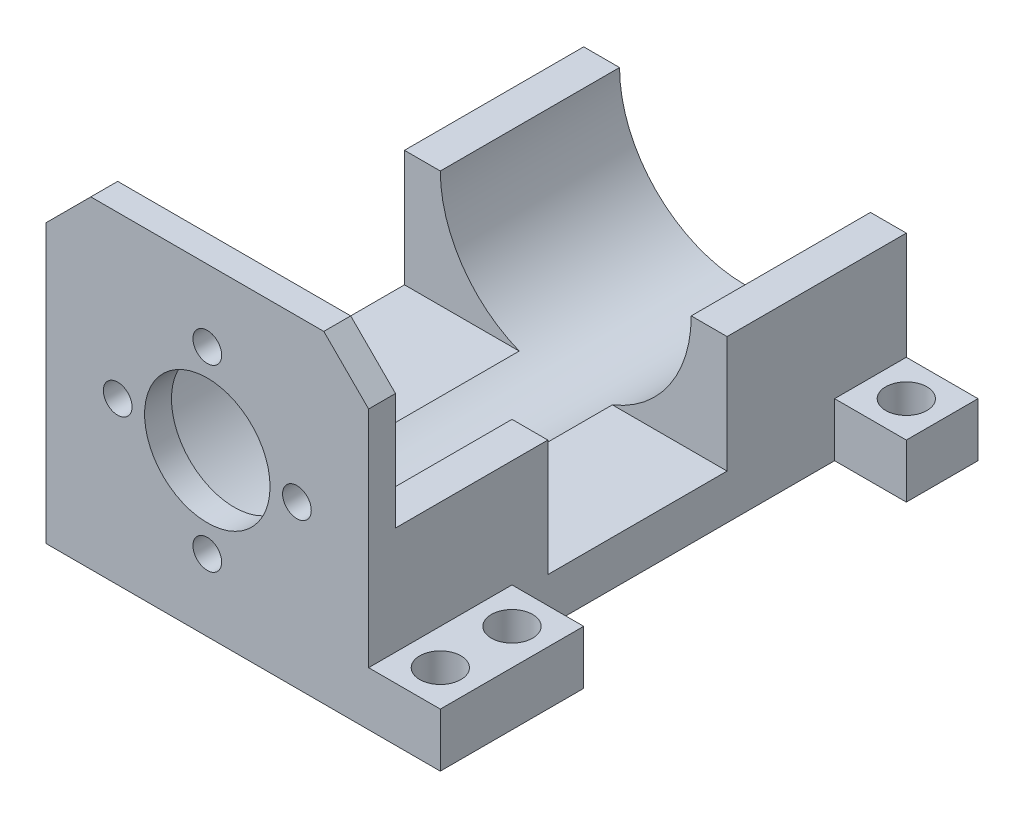
SolidWorks part; units mm, degrees
note: The reader was unsure of these and kept them because the rebuilt part matched: shared geometry of "Esquisse1<3>".
ref_plane "Plan de face" through (0, 0, 0) normal (0, 0, 1) x (1, 0, 0)
ref_plane "Plan de dessus" through (0, 0, 0) normal (0, 1, 0) x (1, 0, 0)
ref_plane "Plan de droite" through (0, 0, 0) normal (1, 0, 0) x (0, 0, -1)
sketch "Esquisse1" plane through (0, 0, 0) normal (0, 0, 1) x (1, 0, 0)
  line L0 (0, 0) -> (-10, 0) construction
  line L1 (-10, 0) -> (10, 0) construction
  line L2 (10, 0) -> (0, 0) construction
  line L3 (0, 0) -> (0, 10) construction
  line L4 (0, 0) -> (0, -10) construction
  line L5 (-18, 0) -> (-18, -18)
  line L6 (-18, -18) -> (0, -18)
  line L7 (0, -18) -> (18, -18)
  line L8 (18, -18) -> (18, 0)
  line L10 (18, 18) -> (-18, 18)
  line L11 (-18, 18) -> (-18, 0)
  line L12 (-18, 18) -> (-18, 13)
  line L13 (-18, 13) -> (-18, 18)
  line L14 (-18, 18) -> (-13, 18)
  line L15 (-13, 18) -> (-18, 13)
  line L16 (18, 18) -> (13, 18)
  line L17 (13, 18) -> (18, 18)
  line L18 (18, 18) -> (18, 13)
  line L19 (18, 13) -> (18, 0)
  line L20 (13, 18) -> (18, 13)
  line L21 (-18, 0) -> (-14, 0)
  line L22 (18, 0) -> (14, 0)
  circle A0 centre (0, 0) radius 14
  circle A1 centre (0, 0) radius 18
  circle A2 centre (-10, 0) radius 1.6
  circle A3 centre (0, 10) radius 1.6
  circle A4 centre (10, 0) radius 1.6
  circle A5 centre (0, -10) radius 1.6
  circle A6 centre (0, 0) radius 7
extrude "Boss.-Extru.1" add sketch "Esquisse1" against normal blind 60 contours A1 L7 L8 | A1 L5 L6 | L21 A1 L22 A0
extrude "Boss.-Extru.2" add sketch "Esquisse1<3>" against normal blind 3 contours A0 A5 A4 A3 A2 | L22 A1 L21 A0 | A1 L19 L20 L10 | A1 L10 L15 L11
sketch "Esquisse1<3>" plane through (0, 0, 0) normal (0, 0, 1) x (1, 0, 0) same geometry as "Esquisse1"
sketch "Esquisse2" plane through (0, -18, 0) normal (0, -1, 0) x (1, 0, 0)
  line L0 (18, 0) -> (26, 0)
  line L1 (26, 0) -> (26, -16)
  line L2 (26, -16) -> (18, -16)
  line L3 (18, -60) -> (18, 0) construction
  line L4 (18, -16) -> (18, 0)
  line L5 (18, -8) -> (26, -8) construction
  line L6 (26, -8) -> (18, 0) construction
  line L7 (26, 0) -> (18, -8) construction
  line L8 (18, -8) -> (26, -16) construction
  line L9 (18, -16) -> (26, -8) construction
  line L10 (26, -8) -> (18, -8) construction
  line L11 (18, -8) -> (18, -60)
  line L12 (18, -60) -> (26, -60)
  line L13 (26, -60) -> (26, -52)
  line L14 (26, -52) -> (18, -52)
  line L15 (18, -52) -> (18, -60) construction
  line L16 (18, -60) -> (26, -52) construction
  line L17 (26, -52) -> (18, -52) construction
  line L18 (18, -52) -> (26, -60) construction
  line L19 (26, -60) -> (-18, -60) construction
  line L20 (-18, -60) -> (-30, -60)
  line L21 (-30, -60) -> (-30, -52)
  line L22 (-30, -52) -> (-18, -52)
  line L23 (-18, -60) -> (-18, 0) construction
  line L24 (-18, -52) -> (-18, -60)
  line L25 (-30, -52) -> (-22, -52) construction
  line L26 (-30, -52) -> (-30, -60) construction
  line L27 (-22, -52) -> (-22, -60) construction
  line L28 (-22, -60) -> (-30, -52) construction
  line L29 (-30, -60) -> (-22, -52) construction
  circle A1 centre (22, -56) radius 2.3
  circle A2 centre (22, -12) radius 2.3
  circle A3 centre (22, -4) radius 2.3
  circle A4 centre (-26, -56) radius 2.3
sketch "Esquisse3" plane through (-18, 0, 0) normal (-1, 0, 0) x (0, 0, 1)
  line L0 (-60, -18) -> (0, -18) construction
  line L1 (-30, -18) -> (-30, 0) construction
  line L2 (-60, 0) -> (-3, 0) construction
  line L3 (-30, 0) -> (-20, 0)
  line L4 (-30, 0) -> (-40, 0)
  line L5 (-40, 0) -> (-40, -18) construction
  line L6 (-40, -18) -> (-30, -18) construction
  line L7 (-30, -18) -> (-20, -18) construction
  line L8 (-20, -18) -> (-20, 0) construction
  line L9 (-40, -18) -> (-40, -13) construction
  line L10 (-40, -13) -> (-20, -13)
  line L11 (-20, -13) -> (-20, 0)
  line L12 (-40, -13) -> (-40, 0)
extrude "Enlèv. mat.-Extru.2" cut sketch "Esquisse3" against normal blind 50
extrude "Boss.-Extru.4" add sketch "Esquisse2" against normal blind 6
